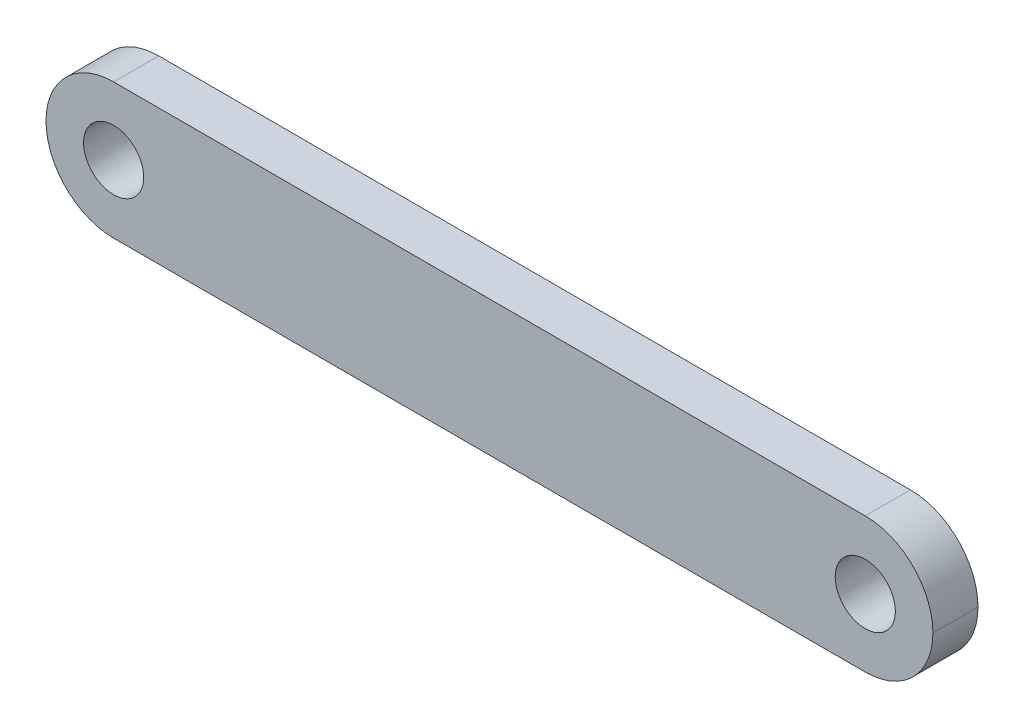
SolidWorks part; units mm, degrees
ref_plane "Front" through (0, 0, 0) normal (0, 0, 1) x (1, 0, 0)
ref_plane "Top" through (0, 0, 0) normal (0, 1, 0) x (1, 0, 0)
ref_plane "Right" through (0, 0, 0) normal (1, 0, 0) x (0, 0, -1)
sketch "Esquisse1" plane through (0, 0, 0) normal (0, 0, 1) x (1, 0, 0)
  line L0 (0, 9) -> (9, 9) construction
  line L1 (0, 0) -> (118, 0)
  line L2 (0, 0) -> (0, 18)
  line L3 (0, 18) -> (118, 18)
  line L4 (118, 0) -> (118, 18)
  line L5 (59, 0) -> (59, 18) construction
  circle A0 centre (9, 9) radius 4
  circle A1 centre (109, 9) radius 4
  dimension "D2" = 8
  dimension "D4" = 100
  dimension "D1" = 18
  dimension "D3" = 9
extrude "Boss.-Extru.1" add sketch "Esquisse1" along normal blind 6
fillet "Congé1" radius 9 4 edges at (118, 18, 3) (118, 0, 3) (0, 0, 3) (0, 18, 3)
